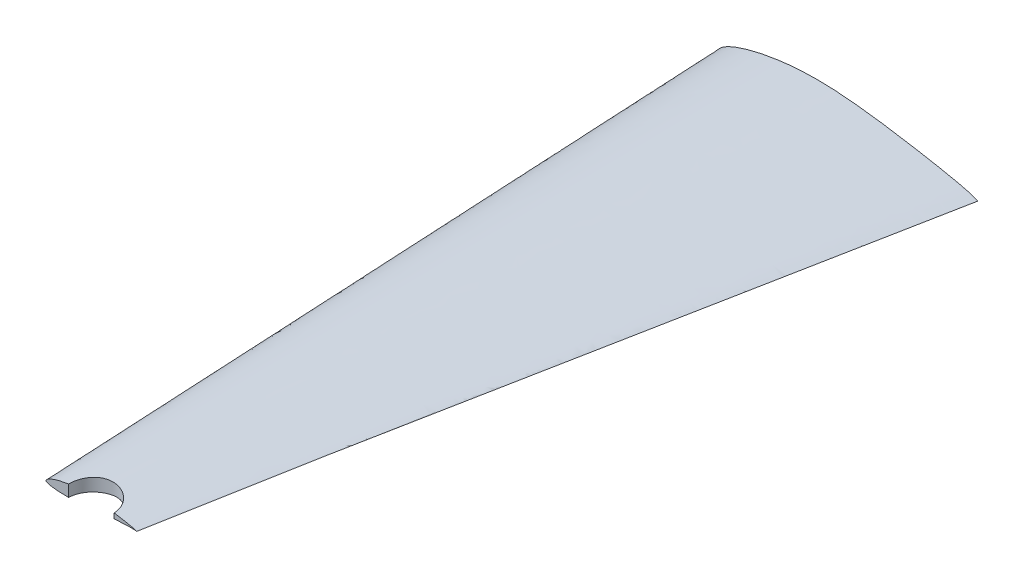
SolidWorks part; units mm, degrees
ref_plane "Front Plane" through (0, 0, 0) normal (0, 0, 1) x (1, 0, 0)
ref_plane "Top Plane" through (0, 0, 0) normal (0, 1, 0) x (1, 0, 0)
ref_plane "Right Plane" through (0, 0, 0) normal (1, 0, 0) x (0, 0, -1)
curve "Curve1"
  spline degree 3 poles (0.9921, 0.0008, 0) (1.0019, -0.0008, 0) (0.9929, 0.0016, 0) (0.9861, 0.0043, 0) (0.9706, 0.0096, 0) (0.9519, 0.0152, 0) (0.9278, 0.021, 0) (0.8992, 0.0273, 0) (0.8662, 0.0341, 0) (0.8293, 0.0413, 0) (0.789, 0.0488, 0) (0.746, 0.0564, 0) (0.7007, 0.0641, 0) (0.6538, 0.0714, 0) (0.6058, 0.0784, 0) (0.5573, 0.0846, 0) (0.5088, 0.0898, 0) (0.4609, 0.0938, 0) (0.4138, 0.0961, 0) (0.3679, 0.0966, 0) (0.3232, 0.0952, 0) (0.2801, 0.092, 0) (0.2388, 0.0874, 0) (0.1997, 0.0815, 0) (0.1631, 0.0746, 0) (0.1296, 0.0669, 0) (0.0993, 0.0585, 0) (0.0726, 0.0496, 0) (0.0499, 0.0404, 0) (0.0312, 0.031, 0) (0.0168, 0.0217, 0) (0.0085, 0.0145, 0) (0.0039, 0.009, 0) (0.0018, 0.0058, 0) (0.0004, 0.0024, 0) (0, 0.0003, 0) (0, -0.0012, 0) (0.0006, -0.0026, 0) (0.002, -0.0043, 0) (0.0049, -0.007, 0) (0.0107, -0.0108, 0) (0.0215, -0.0156, 0) (0.0378, -0.0206, 0) (0.0598, -0.0253, 0) (0.0864, -0.0294, 0) (0.1174, -0.033, 0) (0.1523, -0.036, 0) (0.1908, -0.0383, 0) (0.2323, -0.0397, 0) (0.2764, -0.0402, 0) (0.3228, -0.0395, 0) (0.3711, -0.0373, 0) (0.4212, -0.0335, 0) (0.4729, -0.0284, 0) (0.526, -0.0227, 0) (0.5798, -0.0169, 0) (0.6336, -0.0114, 0) (0.6866, -0.0064, 0) (0.7378, -0.0023, 0) (0.7866, 0.0009, 0) (0.832, 0.0031, 0) (0.8733, 0.0042, 0) (0.9096, 0.0045, 0) (0.9406, 0.0038, 0) (0.9645, 0.0029, 0) (0.984, 0.0013, 0) (0.9921, 0.0008, 0) (1.0019, -0.0008, 0) (0.9929, 0.0016, 0) knots -0.016161 -0.007282 -0.001839 0 0.00178 0.006777 0.014308 0.024046 0.036116 0.050547 0.06713 0.085624 0.105767 0.127282 0.149864 0.17323 0.197069 0.221103 0.245052 0.268663 0.291773 0.314299 0.336178 0.357377 0.377792 0.397225 0.415489 0.432417 0.447849 0.461651 0.473687 0.483898 0.492263 0.498797 0.499955 0.502811 0.504371 0.50536 0.505925 0.506503 0.507535 0.509205 0.512345 0.517665 0.526422 0.537425 0.550643 0.565966 0.583206 0.602155 0.622587 0.644255 0.666998 0.690703 0.715307 0.740824 0.767084 0.793717 0.820331 0.846519 0.871863 0.895937 0.918335 0.938667 0.956573 0.971715 0.983839 0.992718 0.998161 1 1.00178 1.006777 1.014308 periodic
sketch "Sketch1" plane through (0, 0, 0) normal (0, 0, 1) x (1, 0, 0)
  line L0 (1122.2059, -30.8288) -> (-1162.7941, -35.0845) construction
  spline S1 degree 3 poles (1104.1363, -28.0222) (1126.6295, -31.7875) (1105.8826, -26.3024) (1090.4575, -20.1288) (1054.9513, -7.9956) (1012.296, 4.6638) (957.0478, 17.8508) (891.7164, 32.0367) (816.2153, 47.3864) (731.9108, 63.6705) (639.9041, 80.612) (541.5101, 97.9168) (438.0076, 115.0958) (330.7593, 131.7488) (221.0675, 147.3336) (110.2357, 161.251) (-0.493, 172.9975) (-110.0556, 181.8587) (-217.6516, 186.9061) (-322.6724, 187.859) (-424.6755, 184.4831) (-523.1626, 176.9995) (-617.5035, 166.1709) (-706.8843, 152.6667) (-790.3524, 136.737) (-867.0563, 118.889) (-936.2082, 99.5088) (-997.0691, 79.0242) (-1049.0447, 57.9028) (-1091.6336, 36.4479) (-1124.4686, 15.1943) (-1143.3869, -1.4067) (-1153.8659, -14.0298) (-1158.6984, -21.3016) (-1161.9612, -29.0988) (-1162.8988, -33.8887) (-1162.7223, -37.2464) (-1161.3764, -40.4052) (-1158.2301, -44.4654) (-1151.5185, -50.6376) (-1138.2079, -59.2164) (-1113.635, -70.0567) (-1076.2399, -81.3981) (-1026.0446, -92.1031) (-965.2298, -101.4019) (-894.4776, -109.4657) (-814.6314, -116.0953) (-726.7099, -121.1028) (-631.8133, -124.2931) (-530.9633, -125.2112) (-425.0342, -123.2363) (-314.6436, -117.9744) (-200.1569, -109.1265) (-81.9663, -97.1903) (39.2548, -83.9633) (162.1641, -70.4688) (285.0306, -57.6215) (406.0083, -46.0046) (523.1884, -36.2734) (634.6311, -28.7415) (738.3789, -23.5277) (832.7109, -20.7776) (915.5317, -20.0924) (986.36, -21.3847) (1040.9806, -23.338) (1085.6437, -26.9173) (1104.1363, -28.0222) (1126.6295, -31.7875) (1105.8826, -26.3024) knots -0.016161 -0.007282 -0.001839 0 0.00178 0.006777 0.014308 0.024046 0.036116 0.050547 0.06713 0.085624 0.105767 0.127282 0.149864 0.17323 0.197069 0.221103 0.245052 0.268663 0.291773 0.314299 0.336178 0.357377 0.377792 0.397225 0.415489 0.432417 0.447849 0.461651 0.473687 0.483898 0.492263 0.498797 0.499955 0.502811 0.504371 0.50536 0.505925 0.506503 0.507535 0.509205 0.512345 0.517665 0.526422 0.537425 0.550643 0.565966 0.583206 0.602155 0.622587 0.644255 0.666998 0.690703 0.715307 0.740824 0.767084 0.793717 0.820331 0.846519 0.871863 0.895937 0.918335 0.938667 0.956573 0.971715 0.983839 0.992718 0.998161 1 1.00178 1.006777 1.014308 only from (1122.2059, -30.8288) to (1122.2059, -30.8288)
  dimension "D1" = 2285
ref_plane "Plane1" through (0, 0, 6200) normal (0, 0, 1) x (1, 0, 0)
ref_plane "Plane3" through (0, -35.0845, 0) normal (0, 1, 0) x (1, 0, 0)
sketch "Sketch4" plane through (0, -35.0845, 0) normal (0, 1, 0) x (1, 0, 0)
  line L1 (1122.2059, 0) -> (-1162.7941, 0) construction
  line L2 (-172.1886, -6200) -> (172.1886, -6200) construction
  line L4 (-1162.7941, 0) -> (-862.7941, -6200)
sketch "Sketch5" plane through (0, 0, 6200) normal (0, 0, 1) x (1, 0, 0)
  line L0 (-62.749, -35.2354) -> (-862.7688, -35.3009) construction
  spline S1 degree 3 poles (-69.0897, -34.3504) (-61.22, -35.5469) (-68.4893, -33.741) (-73.9048, -31.6671) (-86.3598, -27.6181) (-101.3126, -23.4229) (-120.663, -19.1093) (-143.5377, -14.4998) (-169.9677, -9.5373) (-199.4749, -4.2947) (-231.6736, 1.1372) (-266.1033, 6.6624) (-302.3153, 12.1171) (-339.8318, 17.3686) (-378.1955, 22.2345) (-416.9483, 26.5125) (-455.6538, 30.0335) (-493.9373, 32.5536) (-531.5145, 33.7529) (-568.1715, 33.5367) (-603.7528, 31.8256) (-638.0855, 28.6992) (-670.9538, 24.4271) (-702.0769, 19.2472) (-731.124, 13.2516) (-757.8002, 6.6219) (-781.8329, -0.5031) (-802.9662, -7.9701) (-820.9952, -15.6131) (-835.7466, -23.3233) (-847.0949, -30.9123) (-853.6106, -36.8049) (-857.2018, -41.2651) (-858.8503, -43.8282) (-859.9483, -46.5664) (-860.2505, -48.243) (-860.1714, -49.4139) (-859.6851, -50.5093) (-858.5659, -51.9099) (-856.1913, -54.0289) (-851.5011, -56.9533) (-842.8685, -60.6082) (-829.7584, -64.3709) (-812.1844, -67.8447) (-790.9116, -70.7722) (-766.1771, -73.2167) (-738.2762, -75.1133) (-707.5656, -76.4015) (-674.4302, -77.0191) (-639.2289, -76.8125) (-602.2702, -75.5698) (-563.7715, -73.1566) (-523.8621, -69.4706) (-482.6761, -64.6873) (-440.4393, -59.4377) (-397.6147, -54.086) (-354.8016, -48.9603) (-312.6413, -44.2739) (-271.7964, -40.2655) (-232.9425, -37.0546) (-196.7619, -34.6929) (-163.8546, -33.2402) (-134.9538, -32.5684) (-110.2281, -32.6493) (-91.1554, -33.0456) (-75.5494, -34.0614) (-69.0897, -34.3504) (-61.22, -35.5469) (-68.4893, -33.741) knots -0.016161 -0.007282 -0.001839 0 0.00178 0.006777 0.014308 0.024046 0.036116 0.050547 0.06713 0.085624 0.105767 0.127282 0.149864 0.17323 0.197069 0.221103 0.245052 0.268663 0.291773 0.314299 0.336178 0.357377 0.377792 0.397225 0.415489 0.432417 0.447849 0.461651 0.473687 0.483898 0.492263 0.498797 0.499955 0.502811 0.504371 0.50536 0.505925 0.506503 0.507535 0.509205 0.512345 0.517665 0.526422 0.537425 0.550643 0.565966 0.583206 0.602155 0.622587 0.644255 0.666998 0.690703 0.715307 0.740824 0.767084 0.793717 0.820331 0.846519 0.871863 0.895937 0.918335 0.938667 0.956573 0.971715 0.983839 0.992718 0.998161 1 1.00178 1.006777 1.014308 only from (-62.7688, -35.2354) to (-62.7688, -35.2354)
  dimension "D1" = 800
sketch "Sketch6" plane through (0, 0, 6200) normal (0, 0, 1) x (1, 0, 0)
  line L0 (-862.7688, -35.3009) -> (-860.1517, -49.246)
  spline S0 degree 3 poles (-69.0897, -34.3504) (-61.22, -35.5469) (-68.4893, -33.741) (-73.9048, -31.6671) (-86.3598, -27.6181) (-101.3126, -23.4229) (-120.663, -19.1093) (-143.5377, -14.4998) (-169.9677, -9.5373) (-199.4749, -4.2947) (-231.6736, 1.1372) (-266.1033, 6.6624) (-302.3153, 12.1171) (-339.8318, 17.3686) (-378.1955, 22.2345) (-416.9483, 26.5125) (-455.6538, 30.0335) (-493.9373, 32.5536) (-531.5145, 33.7529) (-568.1715, 33.5367) (-603.7528, 31.8256) (-638.0855, 28.6992) (-670.9538, 24.4271) (-702.0769, 19.2472) (-731.124, 13.2516) (-757.8002, 6.6219) (-781.8329, -0.5031) (-802.9662, -7.9701) (-820.9952, -15.6131) (-835.7466, -23.3233) (-847.0949, -30.9123) (-853.6106, -36.8049) (-857.2018, -41.2651) (-858.8503, -43.8282) (-859.9483, -46.5664) (-860.2505, -48.243) (-860.1714, -49.4139) (-859.6851, -50.5093) (-858.5659, -51.9099) (-856.1913, -54.0289) (-851.5011, -56.9533) (-842.8685, -60.6082) (-829.7584, -64.3709) (-812.1844, -67.8447) (-790.9116, -70.7722) (-766.1771, -73.2167) (-738.2762, -75.1133) (-707.5656, -76.4015) (-674.4302, -77.0191) (-639.2289, -76.8125) (-602.2702, -75.5698) (-563.7715, -73.1566) (-523.8621, -69.4706) (-482.6761, -64.6873) (-440.4393, -59.4377) (-397.6147, -54.086) (-354.8016, -48.9603) (-312.6413, -44.2739) (-271.7964, -40.2655) (-232.9425, -37.0546) (-196.7619, -34.6929) (-163.8546, -33.2402) (-134.9538, -32.5684) (-110.2281, -32.6493) (-91.1554, -33.0456) (-75.5494, -34.0614) (-69.0897, -34.3504) (-61.22, -35.5469) (-68.4893, -33.741) knots -0.016161 -0.007282 -0.001839 0 0.00178 0.006777 0.014308 0.024046 0.036116 0.050547 0.06713 0.085624 0.105767 0.127282 0.149864 0.17323 0.197069 0.221103 0.245052 0.268663 0.291773 0.314299 0.336178 0.357377 0.377792 0.397225 0.415489 0.432417 0.447849 0.461651 0.473687 0.483898 0.492263 0.498797 0.499955 0.502811 0.504371 0.50536 0.505925 0.506503 0.507535 0.509205 0.512345 0.517665 0.526422 0.537425 0.550643 0.565966 0.583206 0.602155 0.622587 0.644255 0.666998 0.690703 0.715307 0.740824 0.767084 0.793717 0.820331 0.846519 0.871863 0.895937 0.918335 0.938667 0.956573 0.971715 0.983839 0.992718 0.998161 1 1.00178 1.006777 1.014308 only from (-62.7688, -35.2354) to (-62.7688, -35.2354) construction
ref_axis "Axis2" through (-860.1517, -49.246, 6200) along (-0.0488, 0.0023, -0.9988)
loft "Loft5" add profiles "Sketch1", "Sketch5" connector at (-829.2128, 127.5517, 0) connector at (-729.5824, 13.4038, 6200)
sketch "Sketch9" plane through (0, 0, 0) normal (0, 0, -1) x (-1, 0, 0)
  line L1 (513.5943, 97.9459) -> (666.6195, 97.9459)
  line L2 (513.5943, 97.9459) -> (513.5943, -16.278)
  line L3 (513.5943, -16.278) -> (666.6195, -16.278)
  line L4 (666.6195, 97.9459) -> (666.6195, -16.278)
  line L5 (513.5943, 97.9459) -> (666.6195, -16.278) construction
  line L6 (513.5943, -16.278) -> (666.6195, 97.9459) construction
  point P0 (590.1069, 40.8339)
extrude "Boss-Extrude1" add sketch "Sketch9" along normal blind 30
extrude "Cut-Extrude3" cut sketch "Sketch13" along normal blind 9300
sketch "Sketch13" plane through (-2172.4747, -6356.5137, -7372.8161) normal (0, 1, 0) x (1, 0, 0)
  circle A0 centre (1710.9861, -13572.8161) radius 200
